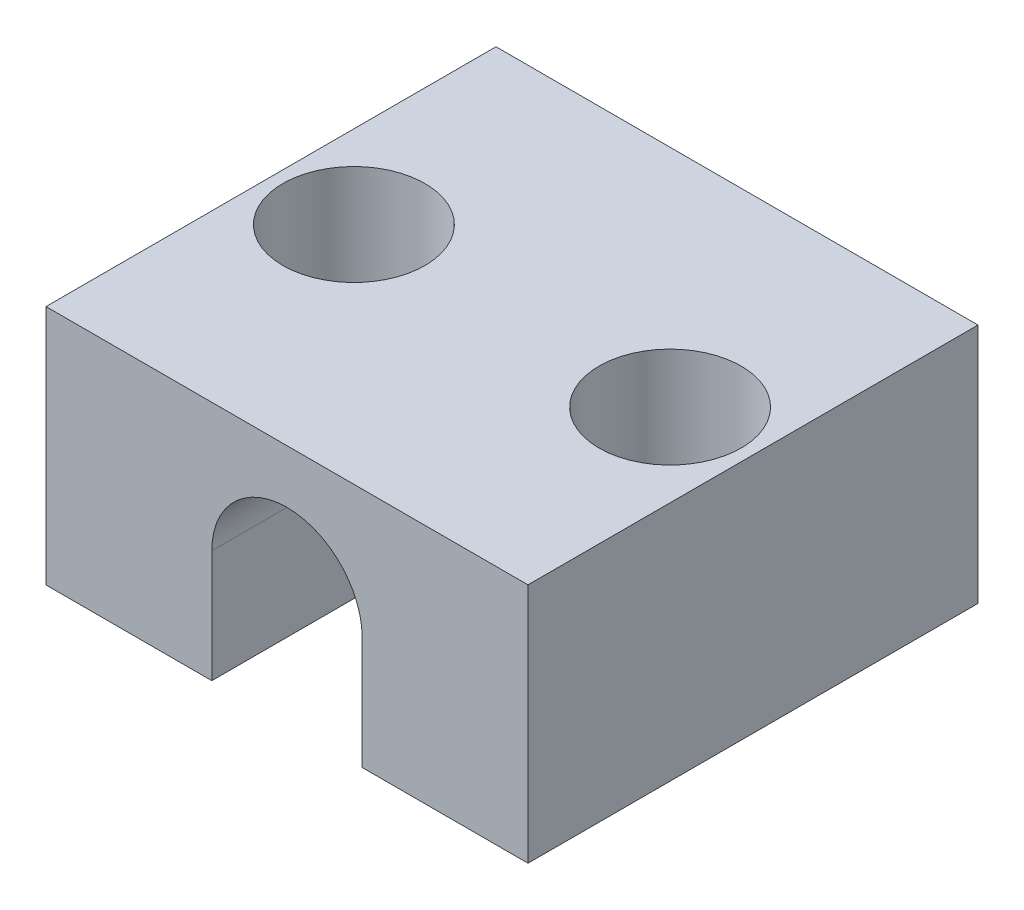
SolidWorks part; units mm, degrees
ref_plane "Front Plane" through (0, 0, 0) normal (0, 0, 1) x (1, 0, 0)
ref_plane "Top Plane" through (0, 0, 0) normal (0, 1, 0) x (1, 0, 0)
ref_plane "Right Plane" through (0, 0, 0) normal (1, 0, 0) x (0, 0, -1)
sketch "Sketch1" plane through (0, 0, 0) normal (0, 0, 1) x (1, 0, 0)
  line L0 (-10.175, 0) -> (-10.175, 10.18)
  line L1 (-10.175, 10.18) -> (10.175, 10.18)
  line L2 (10.175, 10.18) -> (10.175, 0)
  line L3 (-10.175, 0) -> (-3.175, 0)
  line L4 (3.175, 0) -> (10.175, 0)
  line L5 (-3.175, 0) -> (-3.175, 4.75)
  line L6 (3.175, 4.75) -> (3.175, 0)
  arc A2 (-3.175, 4.75) -> (3.175, 4.75) centre (0, 4.75) cw
  dimension "D1" = 3.175
  dimension "D2" = 20.35
  dimension "D3" = 10.18
  dimension "D4" = 7
  dimension "D5" = 4.75
extrude "Boss-Extrude1" add sketch "Sketch1" along normal blind 19
sketch "Sketch2" plane through (0, 10.18, 0) normal (0, 1, 0) x (1, 0, 0)
  line L0 (-6.675, -19) -> (-6.675, 0) construction
  line L1 (-10.175, -19) -> (-3.175, -19) construction
  line L2 (-10.175, 0) -> (-3.175, 0) construction
  line L3 (6.675, 0) -> (6.675, -19) construction
  line L4 (3.175, 0) -> (10.175, 0) construction
  line L5 (3.175, -19) -> (10.175, -19) construction
  circle A0 centre (-6.675, -9.5) radius 1.8
  circle A1 centre (6.675, -9.5) radius 1.8
  circle A2 centre (-6.675, -9.5) radius 3
  circle A3 centre (6.675, -9.5) radius 3
  dimension "D1" = 3.6
  dimension "D2" = 6
extrude "Cut-Extrude1" cut sketch "Sketch2" against normal through all contours A0 | A1 region at (-6.675, 10.18, 9.5)
extrude "Cut-Extrude2" cut sketch "Sketch2<3>" against normal offset from surface (7.18 mm away) 3 contours A2 A0 | A3 region at (-9.5901, 10.18, 9.5) up to face at (-6.675, 0, 11.3)
sketch "Sketch2<3>" plane through (0, 10.18, 0) normal (0, 1, 0) x (1, 0, 0) same geometry as "Sketch2"
sketch "Sketch3" [suppressed] plane through (0, 10.18, 0) normal (0, 1, 0) x (1, 0, 0)
  line L0 (-10.175, 0) -> (-10.175, 50)
  line L1 (-10.175, 50) -> (10.175, 50)
  line L2 (10.175, 0) -> (10.175, 50)
  line L3 (10.175, 0) -> (-10.175, 0) construction
  line L4 (10.175, 0) -> (-10.175, 0)
  line L5 (0, 50) -> (0, 18.5168) construction
  line L6 (-7.5, 44) -> (-6, 44)
  line L7 (-7.5, 44) -> (-7.5, 40)
  line L8 (-7.5, 40) -> (-6, 40)
  line L9 (-6, 44) -> (-6, 40)
  line L10 (6, 44) -> (7.5, 44)
  line L11 (6, 44) -> (6, 40)
  line L12 (6, 40) -> (7.5, 40)
  line L13 (7.5, 44) -> (7.5, 40)
  line L14 (-7.5, 30) -> (-6, 30)
  line L15 (-7.5, 30) -> (-7.5, 26)
  line L16 (-7.5, 26) -> (-6, 26)
  line L17 (-6, 30) -> (-6, 26)
  line L18 (6, 30) -> (7.5, 30)
  line L19 (6, 30) -> (6, 26)
  line L20 (6, 26) -> (7.5, 26)
  line L21 (7.5, 30) -> (7.5, 26)
  dimension "D1" = 50
  dimension "D2" = 1.5
  dimension "D3" = 4
  dimension "D4" = 6
  dimension "D5" = 10
  dimension "D6" = 12
extrude "Boss-Extrude2" [suppressed] add sketch "Sketch3" against normal up to vertex (52.0304 mm away)
